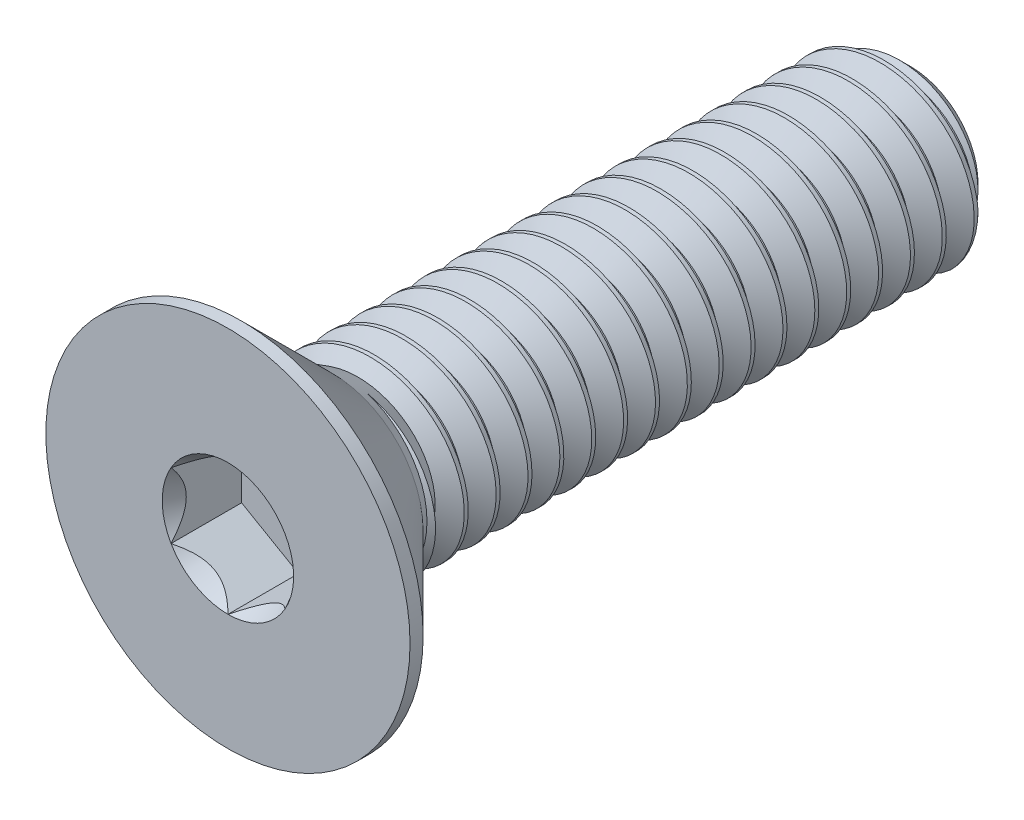
SolidWorks part; units mm, degrees
note: '?' marks a value the reader was unsure of.
ref_plane "Front Plane" through (0, 0, 0) normal (0, 0, 1) x (1, 0, 0)
ref_plane "Top Plane" through (0, 0, 0) normal (0, 1, 0) x (1, 0, 0)
ref_plane "Right Plane" through (0, 0, 0) normal (1, 0, 0) x (0, 0, -1)
sketch "Sketch1" plane through (0, 0, 0) normal (1, 0, 0) x (0, 0, -1)
  line L0 (0, 0) -> (12.7, 0) construction
  line L1 (0, 0) -> (-2.3, 0) construction
  line L2 (-2.3, 4) -> (-2.3, -4) construction
  line L4 (-2.3, 4) -> (-2.0125, 4) construction
  line L5 (12.7, 2) -> (12.7, -2) construction
  line L6 (12.7, 2) -> (12, 2) construction
  line L7 (-2.3, 1.25) -> (-2.3, -1.25) construction
  line L8 (-2.3, 1.25) -> (-0.75, 1.25) construction
  line L9 (-2.0125, 4) -> (1.9875, 0) construction
  line L10 (1.9875, 0) -> (-2.0125, -4) construction
  line L11 (-2.0125, -4) -> (-2.3, -4) construction
  point P6 (-2.3, 0)
  point P8 (10.95, -2)
  point P10 (12.7, 0)
  point P14 (-2.3, 0)
  point P15 (-2.0125, 0)
  point P21 (0, 1.9875)
  dimension "H Ht" = 2.3
  dimension "HD" = 8
  dimension "OD" = 4
  dimension "Pitch" = 0.7
  dimension "Drive" = 2.5
  dimension "Hex D" = 1.55
  dimension "D2" = 0.2875
  dimension "D1" = 90
  dimension "D3" = 1.75
  dimension "L" = 15
sketch "Sketch2" plane through (0, 0, 0) normal (1, 0, 0) x (0, 0, -1)
  line L0 (-2.3, 0) -> (-2.3, 4)
  line L4 (0, 0) -> (-2.3, 0)
  line L5 (-2.3, 4) -> (-2.0125, 4)
  line L6 (-2.0125, 4) -> (0, 1.9875)
  line L7 (-2.0125, 4) -> (1.9875, 0) construction
  line L8 (0, 1.9875) -> (0, 0)
revolve "Revolve1" add sketch "Sketch2" angle 360 about L0
sketch "Sketch3" plane through (0, 0, 0) normal (1, 0, 0) x (0, 0, -1)
  line L0 (12.7, 0) -> (12.7, 1.475)
  line L1 (12.7, 2) -> (12.7, -2) construction
  line L2 (12.7, 1.475) -> (12.175, 2)
  line L3 (12.175, 2) -> (0, 2)
  line L6 (0, 0) -> (12.7, 0) construction
  line L7 (0, 0) -> (12.7, 0)
  line L8 (0, 0) -> (0, 2)
  line L9 (0, 0) -> (0, 4) construction
  dimension "D1" = 45
  dimension "D2" = 0.525
revolve "Revolve2" add sketch "Sketch3" angle 360 about L1
ref_plane "Plane1" through (0, 0, 2.3) normal (0, 0, 1) x (1, 0, 0)
sketch "Sketch5" plane through (0, 0, 2.3) normal (0, 0, 1) x (1, 0, 0)
  line L1 (0, -1.4434) -> (1.25, -0.7217)
  line L2 (1.25, -0.7217) -> (1.25, 0.7217)
  line L3 (1.25, 0.7217) -> (0, 1.4434)
  line L4 (0, 1.4434) -> (-1.25, 0.7217)
  line L5 (-1.25, 0.7217) -> (-1.25, -0.7217)
  line L6 (-1.25, -0.7217) -> (0, -1.4434)
  circle A0 centre (0, 0) radius 1.25 construction
extrude "Cut-Extrude1" cut sketch "Sketch5" against normal up to vertex (1.55 mm away) up to point (0, 1.25, 0.75)
sketch "Sketch6" plane through (0, 0, 2.3) normal (0, 0, 1) x (1, 0, 0)
  circle A0 centre (0, 0) radius 1.4434
extrude "Cut-Extrude2" cut sketch "Sketch6" against normal up to vertex (1.55 mm away) draft 30 up to point (0, 1.25, 0.75)
split "Split1" trim tools "Front Plane" bodies to split 107 resulting bodies 108 109
chamfer "Chamfer1" distance 0.35 angle 45 1 edges at (0, 2, 0)
ref_plane "Plane2" through (0, 0, -12.7) normal (0, 0, 1) x (1, 0, 0)
sketch "Sketch7" plane through (0, 0, -12.7) normal (0, 0, 1) x (1, 0, 0)
  circle A0 centre (0, 0) radius 2
curve "Helix/Spiral1" pitch 0.7 height 18.75 turns 26.7857
sketch "Sketch8" plane through (0, 0, 0) normal (1, 0, 0) x (0, 0, -1)
  line L0 (12.6562, 2.0758) -> (13.3562, 2.0758) construction
  line L1 (13.3562, 2.0758) -> (13.0062, 1.4696) construction
  line L2 (13.0062, 1.4696) -> (12.6562, 2.0758) construction
  line L3 (13.0062, 1.4696) -> (13.0062, 1.5453) construction
  line L4 (13.0062, 1.5453) -> (13.0062, 2) construction
  line L5 (13.0062, 2) -> (13.0062, 2.0758) construction
  line L6 (12.9625, 1.5453) -> (13.05, 1.5453) construction
  line L7 (12.9625, 1.5453) -> (13.05, 1.5453)
  line L8 (12.6781, 2.0379) -> (13.3344, 2.0379) construction
  line L10 (12.7, 2) -> (13.3125, 2) construction
  line L24 (12.9625, 1.5453) -> (12.6781, 2.0379)
  line L25 (12.6781, 2.0379) -> (13.3344, 2.0379)
  line L26 (13.3344, 2.0379) -> (13.05, 1.5453)
  point P8 (13.0062, 2)
  point P13 (13.0062, 2.0379)
  point P14 (13.0062, 2.0379)
  point P15 (13.0062, 1.5453)
  dimension "D1" = 0.7
  dimension "D2" = 0.0875
sweep "Cut-Sweep1" cut profiles "Sketch8" path "Helix/Spiral1"
sketch "Sketch9" plane through (0, 0, 0) normal (0, 0, 1) x (1, 0, 0)
  circle A1 centre (0, 0) radius 1.9875 construction
  circle A2 centre (0, 0) radius 1.9875
extrude "Boss-Extrude1" add sketch "Sketch9" against normal blind 7.5 draft 30.9
ref_axis "Center Axis 1" through (0, 0, 0) along (0, 0, -1)?
ref_plane "Contact Plane 1" through (0, 0, 2.3) normal (0, 0, 1) x (1, 0, 0)
ref_plane "Contact Plane 2" through (0, 0, -12.7) normal (0, 0, -1) x (-1, 0, 0)
equation "\"D2@Sketch3\"=\"Pitch@Sketch1\"*.75"
equation "\"D2@Sketch1\"=\"H Ht@Sketch1\"/8"
equation "\"D4@Helix/Spiral1\"=\"Pitch@Sketch1\""
equation "\"D3@Helix/Spiral1\"=\"L@Sketch1\"*1.25"
equation "\"D1@Sketch8\"=\"Pitch@Sketch1\""
equation "\"D2@Sketch8\"=\"D1@Sketch8\"/8"
equation "\"D3@Sketch1\"=\"Pitch@Sketch1\"*2.5"
equation "\"D1@Chamfer1\" = \"Pitch@Sketch1\" * .5"
equation "\"D1@Boss-Extrude1\"= \"L@Sketch1\" / 2"
